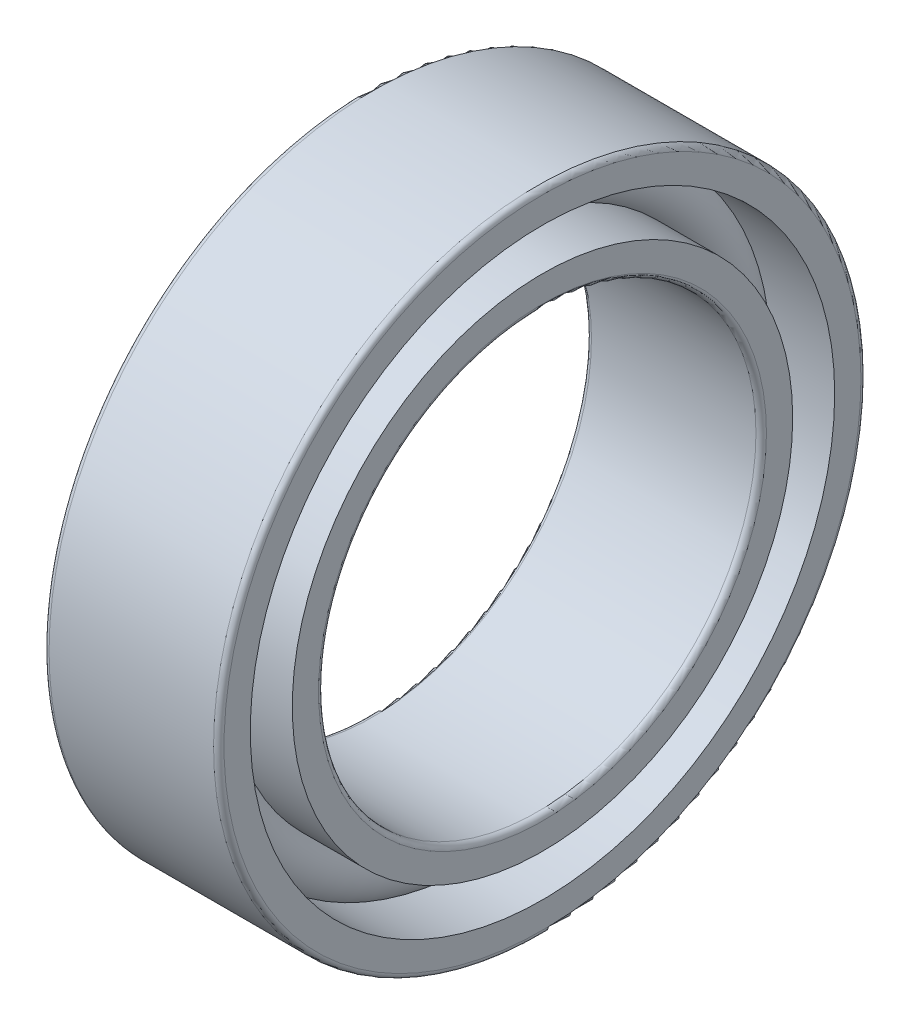
SolidWorks part; units mm, degrees
ref_plane "Plane1" through (0, 0, 0) normal (0, 0, 1) x (1, 0, 0)
ref_plane "Plane2" through (0, 0, 0) normal (0, 1, 0) x (1, 0, 0)
ref_plane "Plane3" through (0, 0, 0) normal (1, 0, 0) x (0, 0, -1)
sketch "Clipboard" plane through (0, 0, 0) normal (0, 0, 1) x (1, 0, 0)
  line L0 (-10, 0) -> (10, 0) construction
  line L1 (0, 0) -> (22.3471, -0.7804)
  line L2 (0, 0) -> (15.4906, 0.5409)
  line L3 (0, 0) -> (22.3471, -0.7804)
  line L4 (0, 0) -> (-22.3573, -0.3902)
  dimension "BallCLRad" = 15.5
sketch "CagSpiSke" plane through (0, 0, 0) normal (0, 0, 1) x (1, 0, 0)
  line L0 (0.18, 15.2) -> (0.18, 15.8)
  line L1 (0.18, 15.8) -> (-0.18, 15.8)
  line L2 (-0.18, 15.8) -> (-0.18, 15.2)
  line L3 (-0.18, 15.2) -> (0.18, 15.2)
  line L4 (-20.6375, 0) -> (20.6375, 0) construction
  line L5 (0, 0) -> (0, 23.7692) construction
  dimension "OD" = 31.6
  dimension "ID" = 30.4
revolve "CageSpine" add sketch "CagSpiSke" angle 0.001 about L4 reverse direction yes
ref_axis "Axis1" through (-50, 0, 0) along (1, 0, 0)
sketch "CagBalSke" plane through (0, 0, 0) normal (0, 0, 1) x (1, 0, 0)
  line L0 (-1.98, 15.5) -> (1.98, 15.5)
  line L1 (-1.905, 15.5) -> (1.905, 15.5) construction
  line L2 (-10, 0) -> (10, 0) construction
  line L3 (0, 0) -> (0, 24) construction
  arc A0 (1.98, 15.5) -> (-1.98, 15.5) centre (0, 15.5) cw
  dimension "BallCLRad" = 15.5
revolve "CageBall" [suppressed] add sketch "CagBalSke" angle 360 about L1 reverse direction yes
pattern_circular "CageBalls" [suppressed] count 2 every 180 about axis through (-50, 0, 0) along (1, 0, 0)
sketch "CagTrmODSke" plane through (0, 0, 0) normal (0, 0, 1) x (1, 0, 0)
  line L0 (1.981, 15.8) -> (1.981, 17.481)
  line L1 (1.981, 17.481) -> (-1.981, 17.481)
  line L2 (-1.981, 17.481) -> (-1.981, 15.8)
  line L3 (-1.981, 15.8) -> (1.981, 15.8)
  line L4 (-20.6375, 0) -> (20.6375, 0) construction
  line L5 (0, 0) -> (0, 25) construction
  dimension "Width" = 3.962
  dimension "ID" = 31.6
  dimension "OD" = 34.962
revolve "CageTrimOD" [suppressed] cut sketch "CagTrmODSke" angle 360 about L4 reverse direction yes
sketch "CagTrmIDSke" plane through (0, 0, 0) normal (0, 0, 1) x (1, 0, 0)
  line L0 (1.981, 13.521) -> (1.981, 15.2)
  line L1 (1.981, 15.2) -> (-1.981, 15.2)
  line L2 (-1.981, 15.2) -> (-1.981, 13.521)
  line L3 (-1.981, 13.521) -> (1.981, 13.521)
  line L4 (-20.6375, 0) -> (20.6375, 0) construction
  line L5 (0, 0) -> (0, 25) construction
  dimension "Width" = 3.962
  dimension "ID" = 27.042
  dimension "OD" = 30.4
revolve "CageTrimID" [suppressed] cut sketch "CagTrmIDSke" angle 360 about L4 reverse direction yes
sketch "BalSimSke" plane through (0, 0, 0) normal (0, 0, 1) x (1, 0, 0)
  line L0 (-10, 0) -> (10, 0) construction
  line L1 (-10, 15.5) -> (10, 15.5) construction
  line L2 (0, 0) -> (0, 23) construction
  circle A0 centre (0, 15.5) radius 1.8
  dimension "BallCLRad" = 15.5
  dimension "Ball_diameter" = 3.6
revolve "BallsSimplified" add sketch "BalSimSke" angle 360 about L0
sketch "BalDetSke" plane through (0, 0, 0) normal (0, 0, 1) x (1, 0, 0)
  line L0 (-1.8, 15.5) -> (1.8, 15.5)
  line L1 (-1.905, 15.5) -> (1.905, 15.5) construction
  line L2 (0, 0) -> (0, 25) construction
  arc A0 (1.8, 15.5) -> (-1.8, 15.5) centre (0, 15.5) cw
  dimension "BallCLRad" = 15.5
  dimension "Ball_diameter" = 3.6
revolve "BallDetailed" [suppressed] add sketch "BalDetSke" angle 360 about L1 reverse direction yes
sketch "InnRacSke" plane through (0, 0, 0) normal (0, 0, 1) x (1, 0, 0)
  line L0 (-1.3079, 14.3) -> (-5, 14.3)
  line L1 (-5, 14.3) -> (-5, 12.8)
  line L2 (-4.7, 12.5) -> (4.7, 12.5)
  line L3 (5, 12.8) -> (5, 14.3)
  line L4 (5, 14.3) -> (1.3079, 14.3)
  line L5 (-20.6375, 0) -> (20.6375, 0) construction
  line L6 (0, 0) -> (0, 30) construction
  arc A0 (-5, 12.8) -> (-4.7, 12.5) centre (-4.7, 12.8) ccw
  arc A1 (4.7, 12.5) -> (5, 12.8) centre (4.7, 12.8) ccw
  arc A2 (1.3079, 14.3) -> (-1.3079, 14.3) centre (0, 15.5) cw
  dimension "BallCLRad" = 15.5
  dimension "Fillet_radius" = 0.3
  dimension "Ball_diameter" = 3.55
  dimension "ID" = 25
  dimension "OD" = 28.6
  dimension "Width" = 10
revolve "InnerRace" add sketch "InnRacSke" angle 360 about L5 reverse direction yes
sketch "OutRacSke" plane through (0, 0, 0) normal (0, 0, 1) x (1, 0, 0)
  line L0 (-1.3079, 16.7) -> (-5, 16.7)
  line L1 (-5, 16.7) -> (-5, 18.2)
  line L2 (-4.7, 18.5) -> (4.7, 18.5)
  line L3 (5, 18.2) -> (5, 16.7)
  line L4 (5, 16.7) -> (1.3079, 16.7)
  line L5 (-20.6375, 0) -> (20.6375, 0) construction
  line L6 (0, 0) -> (0, 30) construction
  arc A0 (-5, 18.2) -> (-4.7, 18.5) centre (-4.7, 18.2) cw
  arc A1 (4.7, 18.5) -> (5, 18.2) centre (4.7, 18.2) cw
  arc A2 (1.3079, 16.7) -> (-1.3079, 16.7) centre (0, 15.5) ccw
  dimension "BallCLRad" = 15.5
  dimension "Fillet_radius" = 0.3
  dimension "Ball_diameter" = 3.55
  dimension "Width" = 10
revolve "OuterRace" add sketch "OutRacSke" angle 360 about L5 reverse direction yes
pattern_circular "BallsDetailed" [suppressed] count 2 every 180 about axis through (-50, 0, 0) along (1, 0, 0)
equation "\"BallCLRad@Clipboard\" = ( \"OD@OutRacSke\" + \"ID@InnRacSke\" ) / 4"
equation "\"BallCLRad@BalSimSke\" = \"BallCLRad@Clipboard\""
equation "\"BallCLRad@BalDetSke\" = \"BallCLRad@Clipboard\""
equation "\"BallCLRad@InnRacSke\" = \"BallCLRad@Clipboard\""
equation "\"BallCLRad@OutRacSke\" = \"BallCLRad@Clipboard\""
equation "\"Ball_diameter@InnRacSke\" = \"Ball_diameter@BalDetSke\" - 0.05"
equation "\"Ball_diameter@OutRacSke\" = \"Ball_diameter@BalDetSke\" - 0.05"
equation "\"Ball_diameter@BalSimSke\" = \"Ball_diameter@BalDetSke\""
equation "\"Width@OutRacSke\" = \"Width@InnRacSke\""
equation "\"Fillet_radius@OutRacSke\" = \"Fillet_radius@InnRacSke\""
equation "\"Max_count@Clipboard\" = int( 3.14159265 / atn(( \"Ball_diameter@BalDetSke\" / 2) / sqr( \"BallCLRad@Clipboard\"  *  \"BallCLRad@Clipboard\" - ( \"Ball_diameter@BalDetSke\" / 2) *  ( \"Ball_diameter@BalDetSke\" / 2))))"
equation "\"Max_count@Clipboard\" = ((sgn( \"Max_count@Clipboard\" - \"Count@Clipboard\" )-1)*( \"Max_count@Clipboard\" - \"Count@Clipboard\" ))/-2+ \"Count@Clipboard\""
equation "\"Count@BallsDetailed\" = int( \"Show_count@Clipboard\" ) "
equation "\"Count@BallsDetailed\" = ((sgn( \"Count@BallsDetailed\" - \"Max_count@Clipboard\" )-1)*( \"Count@BallsDetailed\" - \"Max_count@Clipboard\" ))/-2+ \"Max_count@Clipboard\""
equation "\"Count@BallsDetailed\" = ((sgn( \"Count@BallsDetailed\" - \"Min_count@Clipboard\" )+1)*( \"Count@BallsDetailed\" - \"Min_count@Clipboard\"))/2 +\"Min_count@Clipboard\""
equation "\"Angle@BallsDetailed\" = 360.0 / \"Max_count@Clipboard\""
equation "\"BallCLRad@CagBalSke\" = \"BallCLRad@Clipboard\""
equation "\"Count@CageBalls\" = \"Count@BallsDetailed\""
equation "\"Angle@CageBalls\" = \"Angle@BallsDetailed\""
equation "\"Angle@CageSpine\" =  \"Angle@CageBalls\" * ( \"Count@CageBalls\" -1 + int( \"Count@CageBalls\" / \"Max_count@Clipboard\" ) )  + 0.001 -  int( \"Count@CageBalls\" / \"Max_count@Clipboard\" ) * 0.001"
equation "\"Angle@CageSpine\" =  \"Angle@CageSpine\" * int( \"Min_count@Clipboard\" / 2) + int(1 / \"Min_count@Clipboard\")  * 0.001"
equation "\"CageWallOD@CagBalSke\" =  \"Ball_diameter@BalDetSke\" * 1.1"
equation "\"Thickness@CagSpiSke\" =  \"Ball_diameter@BalDetSke\" * 0.1"
equation "\"OD@CagTrmODSke\" = \"BallCLRad@Clipboard\" * 2 + \"CageWallOD@CagBalSke\" + 0.002"
equation "\"ID@CagTrmODSke\" = \"BallCLRad@Clipboard\" * 2 + \"Ball_diameter@BalDetSke\" / 6"
equation "\"OD@CagTrmIDSke\" = \"BallCLRad@Clipboard\" * 2 - \"Ball_diameter@BalDetSke\" / 6"
equation "\"ID@CagTrmIDSke\" = \"BallCLRad@Clipboard\" * 2 - \"CageWallOD@CagBalSke\" + 0.002"
equation "\"OD@CagSpiSke\" = \"ID@CagTrmODSke\""
equation "\"ID@CagSpiSke\" = \"OD@CagTrmIDSke\""
equation "\"Width@CagTrmODSke\" = \"CageWallOD@CagBalSke\" + 0.002"
equation "\"Width@CagTrmIDSke\" = \"CageWallOD@CagBalSke\" + 0.002"
